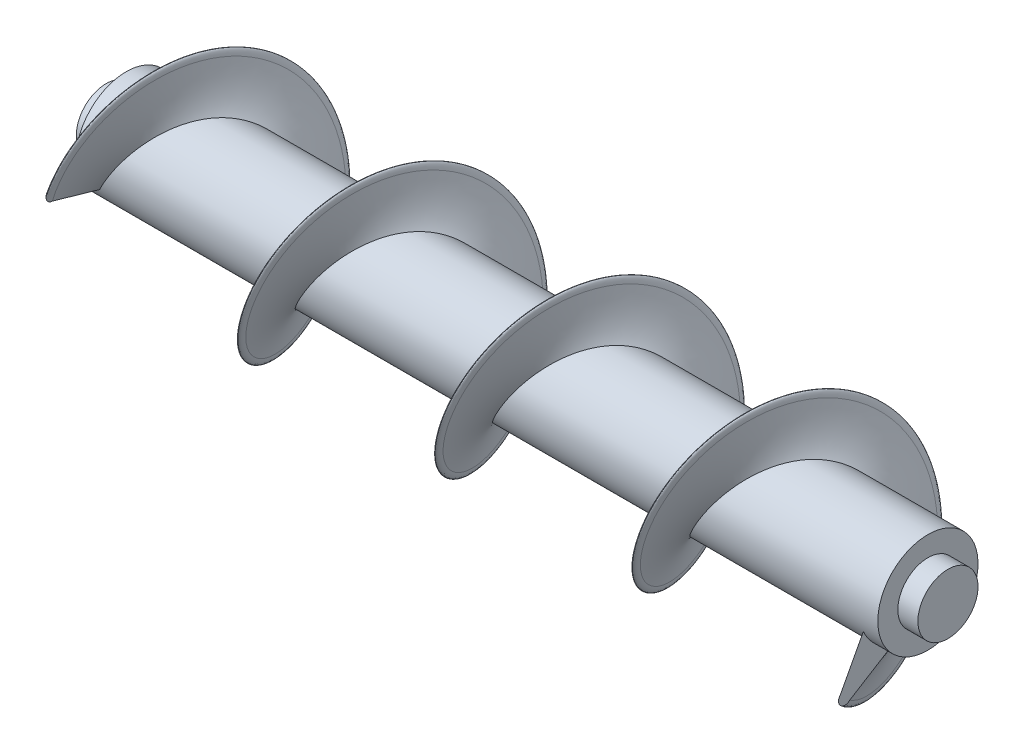
SolidWorks part; units mm, degrees
ref_plane "Front Plane" through (0, 0, 0) normal (0, 0, 1) x (1, 0, 0)
ref_plane "Top Plane" through (0, 0, 0) normal (0, 1, 0) x (1, 0, 0)
ref_plane "Right Plane" through (0, 0, 0) normal (1, 0, 0) x (0, 0, -1)
sketch "Sketch2" plane through (0, 0, 0) normal (0, 0, 1) x (1, 0, 0)
  line L0 (2.54, 0) -> (189.9794, 0) construction
  line L1 (0, 3.7719) -> (0, 6.35)
  line L2 (0, 6.35) -> (101.6, 6.35)
  line L3 (101.6, 6.35) -> (101.6, 3.81)
  line L4 (101.6, 0) -> (2.54, 0)
  line L6 (2.54, 1.4859) -> (2.54, 0)
  line L7 (101.6, 3.81) -> (104.14, 3.81)
  line L8 (104.14, 3.81) -> (104.14, 0)
  line L9 (104.14, 0) -> (101.6, 0)
  line L10 (0, 3.7719) -> (-2.54, 3.7719)
  line L11 (-2.54, 3.7719) -> (-2.54, 1.4859)
  line L12 (2.54, 1.4859) -> (-2.54, 1.4859)
  dimension "D1" = 101.6
  dimension "D2" = 6.35
  dimension "D4" = 1.4859
  dimension "D5" = 3.81
  dimension "D6" = 2.54
  dimension "D7" = 2.54
  dimension "D8" = 2.286
revolve "Revolve7" add sketch "Sketch2" angle 360 about L0
ref_plane "Plane1" through (2.54, 0, 0) normal (-1, 0, 0) x (0, 0, 1)
sketch "Sketch4" plane through (2.54, 0, 0) normal (-1, 0, 0) x (0, 0, 1)
  circle A0 centre (0, 0) radius 12.7
  dimension "D1" = 25.4
curve "Helix/Spiral1" pitch 25 height 96.68 radius 12.7 left hand yes centre (2.54, 0, 0) axis (1, 0, 0) start towards (0, -1, 0)
sketch "Sketch5" plane through (2.54, 0, 0) normal (-1, 0, 0) x (0, 0, 1)
  line L1 (11.8798, 1.0271) -> (5.8106, 2.5611)
  line L2 (11.9069, -0.6399) -> (5.8909, -2.3706)
  arc A0 (12.7001, 0.2067) -> (11.8798, 1.0271) centre (11.8798, 0.2067) ccw
  arc A1 (5.8909, -2.3706) -> (5.8106, 2.5611) centre (0, 0) ccw
  arc A2 (12.7001, 0.2067) -> (11.9069, -0.6399) centre (11.8802, 0.18) cw
sweep "Sweep1" add profiles "Sketch5" path "Helix/Spiral1"
